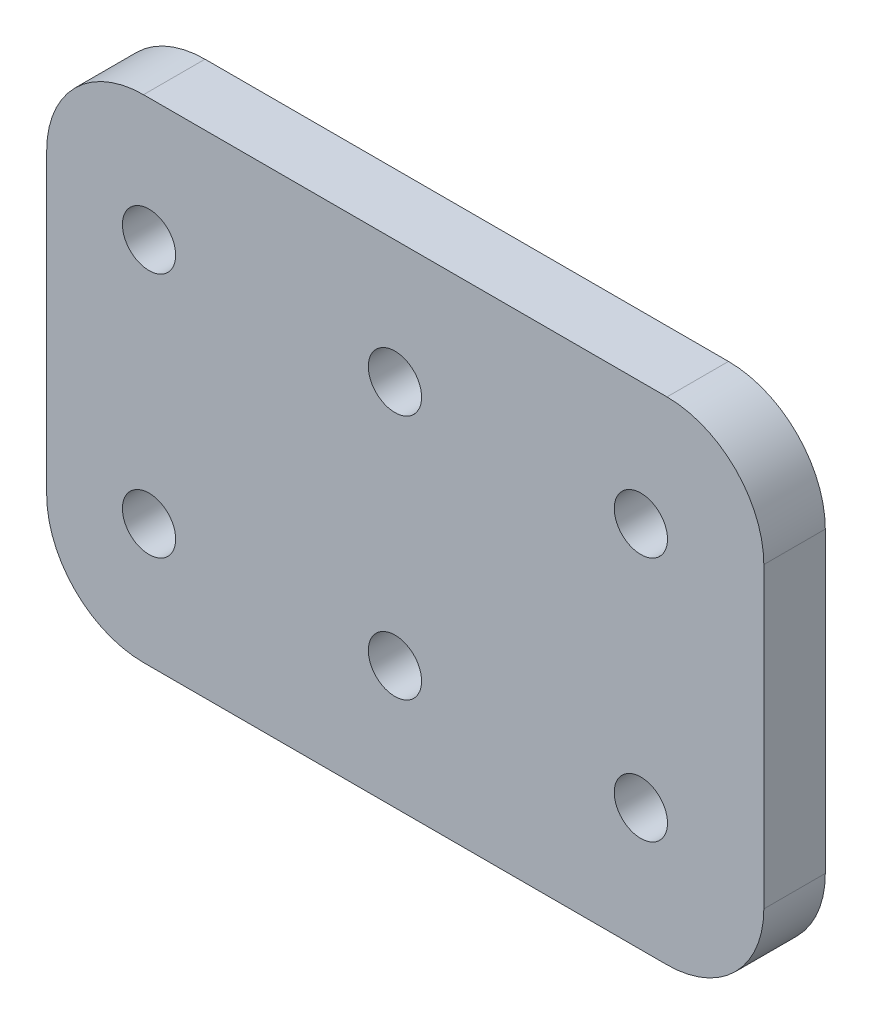
SolidWorks part; units mm, degrees
ref_plane "Front" through (0, 0, 0) normal (0, 0, 1) x (1, 0, 0)
ref_plane "Top" through (0, 0, 0) normal (0, 1, 0) x (1, 0, 0)
ref_plane "Right" through (0, 0, 0) normal (1, 0, 0) x (0, 0, -1)
sketch "Sketch1" plane through (0, 0, 0) normal (0, 0, 1) x (1, 0, 0)
  line L0 (-37.035, 25.4) -> (-39.165, 25.4) construction
  line L1 (37.035, -25.4) -> (-37.035, -25.4)
  line L2 (37.035, -25.4) -> (37.035, 25.4)
  line L3 (37.035, 25.4) -> (-37.035, 25.4)
  line L4 (-37.035, -25.4) -> (-37.035, 25.4)
  line L5 (37.035, -25.4) -> (-37.035, 25.4) construction
  line L6 (37.035, 25.4) -> (-37.035, -25.4) construction
  line L7 (-39.165, 25.4) -> (-39.165, -25.4) construction
  line L8 (-39.165, -25.4) -> (-37.035, -25.4) construction
  line L9 (-13.765, 25.4) -> (-13.765, -25.4) construction
  line L10 (-13.765, 0) -> (-39.165, 0) construction
  line L11 (-26.465, 0) -> (-26.465, 25.4) construction
  line L12 (24.335, 25.4) -> (24.335, -25.4) construction
  line L13 (-1.065, 25.4) -> (-1.065, -25.4) construction
  line L14 (-26.465, 12.7) -> (37.035, 12.7) construction
  line L15 (-26.465, -12.7) -> (37.035, -12.7) construction
  circle A0 centre (-26.465, 12.7) radius 2.5 construction
  circle A1 centre (-26.465, -12.7) radius 2.5 construction
  circle A2 centre (-1.065, 12.7) radius 2.5 construction
  circle A3 centre (24.335, 12.7) radius 2.5 construction
  circle A4 centre (24.335, -12.7) radius 2.5 construction
  circle A5 centre (-1.065, -12.7) radius 2.5 construction
  point P0 (0, 0)
  dimension "D5" = 5
  dimension "D8" = 5
  dimension "D1" = 2.13
  dimension "D2" = 25.4
  dimension "D3" = 50.8
  dimension "D4" = 76.2
  dimension "D6" = 12.7
  dimension "D7" = 25.4
extrude "Boss-Extrude1" add sketch "Sketch1" along normal blind 6.35
fillet "Fillet1" radius 10 4 edges at (-37.035, -25.4, 3.175) (37.035, -25.4, 3.175) (37.035, 25.4, 3.175) (-37.035, 25.4, 3.175)
hole_wizard "M5 Clearance Hole1" positions "Sketch3" profile "Sketch2" hole size "M5" standard "ISO" end condition through all
sketch "Sketch3" plane through (0, 0, 6.35) normal (0, 0, 1) x (1, 0, 0)
  point P0 (-26.465, 12.7)
  point P3 (-26.465, -12.7)
  point P6 (-1.065, -12.7)
  point P9 (-1.065, 12.7)
  point P12 (24.335, 12.7)
  point P15 (24.335, -12.7)
sketch "Sketch2" plane through (-26.465, 12.7, 6.35) normal (1, 0, 0) x (0, -1, 0)
  line L0 (0, 0) -> (0, 6.35)
  line L1 (0, 6.35) -> (2.75, 6.35)
  line L2 (2.75, 6.35) -> (2.75, 0)
  line L5 (2.75, 0) -> (0, 0)
  line L11 (0, -6.35) -> (0, 107.95) construction
  dimension "Thru Hole Dia." = 5.5
  dimension "Thru Hole Depth" = 6.35
